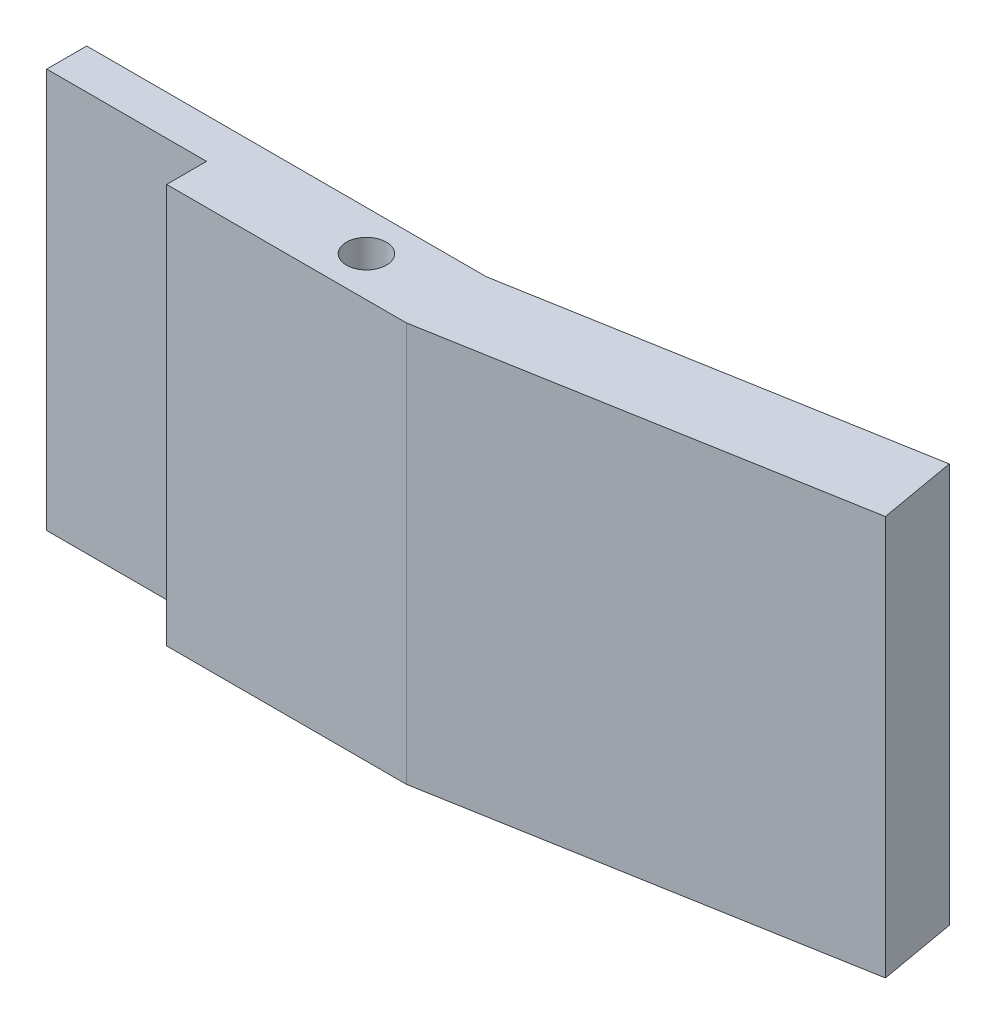
SolidWorks part; units mm, degrees
ref_plane "Front Plane" through (0, 0, 0) normal (0, 0, 1) x (1, 0, 0)
ref_plane "Top Plane" through (0, 0, 0) normal (0, 1, 0) x (1, 0, 0)
ref_plane "Right Plane" through (0, 0, 0) normal (1, 0, 0) x (0, 0, -1)
sketch "Sketch1" plane through (0, 0, 0) normal (0, 1, 0) x (1, 0, 0)
  line L4 (31.75, 0) -> (63.0176, 5.5133)
  line L5 (0, 0) -> (12.7, 0)
  line L6 (0, 0) -> (0, -3.175)
  line L7 (0, -3.175) -> (12.7, -3.175)
  line L8 (12.7, 0) -> (12.7, -3.175)
  line L9 (12.7, 0) -> (31.75, 0)
  line L10 (12.7, 0) -> (12.7, -6.35)
  line L11 (12.7, -6.35) -> (31.75, -6.35)
  line L12 (31.75, 0) -> (31.75, -6.35)
  line L13 (63.0176, 5.5133) -> (64.1036, -0.6452)
  line L14 (64.1036, -0.6452) -> (31.75, -6.35)
  line L15 (31.75, -6.35) -> (64.2, -6.35) construction
  circle A0 centre (25.4, -3.175) radius 1.5875
  point P2 (0, 0)
  dimension "D8" = 3.175
  dimension "D1" = 3.175
  dimension "D2" = 12.7
  dimension "D3" = 6.35
  dimension "D4" = 19.05
  dimension "D5" = 10
  dimension "D6" = 31.75
  dimension "D7" = 25.4
extrude "Boss-Extrude1" add sketch "Sketch1" along normal blind 31.75 contours L14 L13 L4 L12 | L12 L9 L8 L10 L11 | L8 L7 L6 L5 region at (22.0026, 0, 3.175) region at (47.6568, 0, 0.3883)
